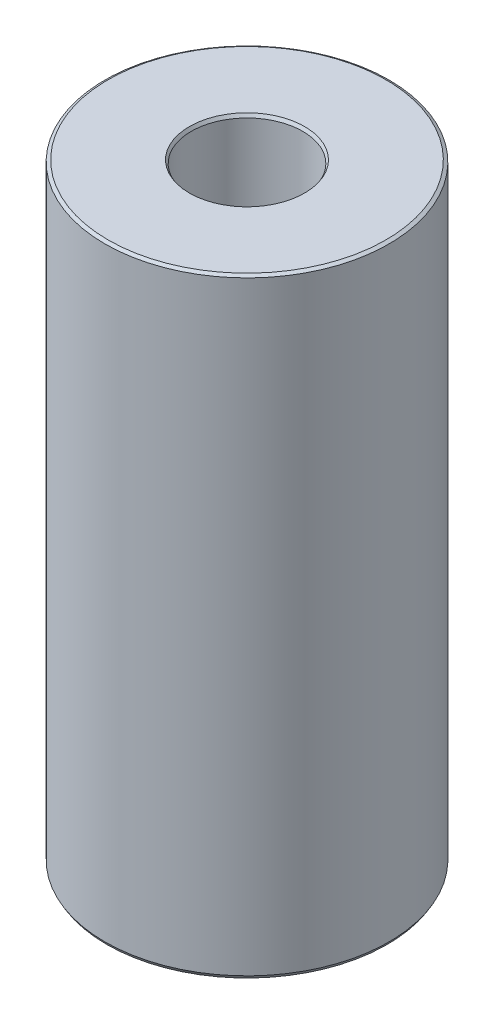
SolidWorks part; units mm, degrees
ref_plane "Front Plane" through (0, 0, 0) normal (0, 0, 1) x (1, 0, 0)
ref_plane "Top Plane" through (0, 0, 0) normal (0, 1, 0) x (1, 0, 0)
ref_plane "Right Plane" through (0, 0, 0) normal (1, 0, 0) x (0, 0, -1)
sketch "Sketch1" plane through (0, 0, 0) normal (0, 1, 0) x (1, 0, 0)
  circle A0 centre (0, 0) radius 22.5
  dimension "SLEEVE_OD" = 45
extrude "Boss-Extrude1" add sketch "Sketch1" along normal blind 96.5479
sketch "Sketch2" plane through (0, 0, 0) normal (0, 1, 0) x (1, 0, 0)
  circle A0 centre (0, 0) radius 8.8372
  dimension "BORE_D" = 17.6744
extrude "Cut-Extrude1" cut sketch "Sketch2" along normal through all
chamfer "Chamfer1" distance 0.2921 angle 60 4 edges at (0, 96.5479, 8.8372) (0, 0, 8.8372) (0, 0, 22.5) (0, 96.5479, 22.5) first distance on face at (0, 96.5479, 8.8372) first distance on face at (0, 0, 8.8372) first distance on face at (0, 96.5479, 22.5)
